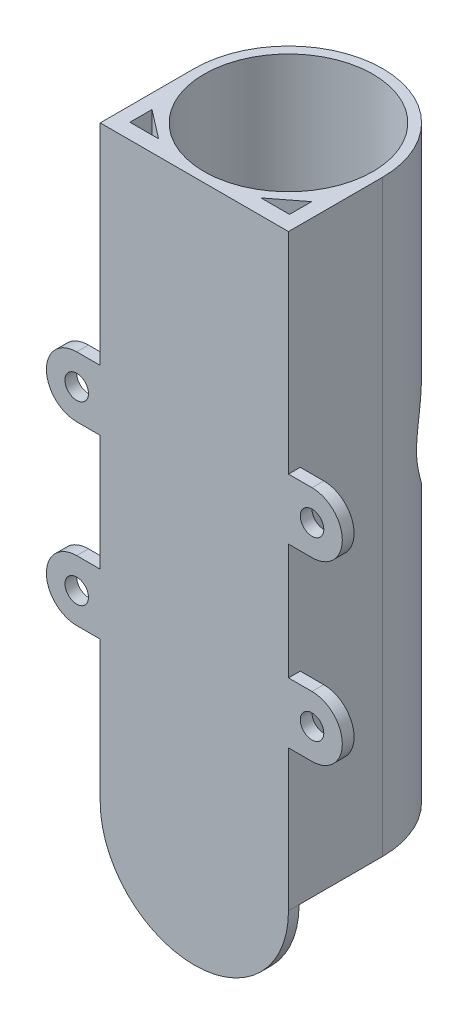
SolidWorks part; units mm, degrees
ref_plane "Front Plane" through (0, 0, 0) normal (0, 0, 1) x (1, 0, 0)
ref_plane "Top Plane" through (0, 0, 0) normal (0, 1, 0) x (1, 0, 0)
ref_plane "Right Plane" through (0, 0, 0) normal (1, 0, 0) x (0, 0, -1)
sketch "Sketch1" plane through (0, 0, 0) normal (0, 1, 0) x (1, 0, 0)
  line L0 (16, -16) -> (-16, -16)
  line L1 (-16, -16) -> (-16, 0)
  line L2 (0, -55) -> (0, 55) construction
  line L3 (16, -16) -> (16, 0)
  line L4 (-13.567, -13.3875) -> (-8.7, -13.3875)
  line L5 (-8.7, -13.3875) -> (-13.567, -9.6312)
  line L6 (-13.567, -9.6312) -> (-13.567, -13.3875)
  line L7 (13.567, -13.3875) -> (8.7, -13.3875)
  line L8 (8.7, -13.3875) -> (13.567, -9.6312)
  line L9 (13.567, -9.6312) -> (13.567, -13.3875)
  arc A0 (16, 0) -> (-16, 0) centre (0, 0) ccw
  circle A1 centre (0, 0) radius 14.35
  point P10 (0, -16)
  dimension "D1" = 32
  dimension "D2" = 1.65
extrude "Boss-Extrude1" add sketch "Sketch1" along normal blind 100
sketch "Sketch2" plane through (0, 0, 16) normal (0, 0, 1) x (1, 0, 0)
  line L0 (0, -55) -> (0, 55) construction
  circle A0 centre (0, 54.8666) radius 13.97
  dimension "D1" = 27.94
extrude "Cut-Extrude3" cut sketch "Sketch2" against normal mid plane 30 from offset 35 offset against normal yes
sketch "Sketch4" plane through (0, 0, 16) normal (0, 0, 1) x (1, 0, 0)
  line L0 (-16, 0) -> (16, 0)
  line L1 (-16, 100) -> (-16, 0) construction
  arc A0 (-16, 0) -> (16, 0) centre (0, 0) ccw
extrude "Boss-Extrude3" add sketch "Sketch4" against normal blind 1.8
sketch "Sketch5" plane through (0, 0, 0) normal (1, 0, 0) x (0, 0, -1)
  line L0 (-14.2, 0) -> (-16, -15.9552)
  line L1 (17.6, 0) -> (-17.6, 0) construction
  line L2 (-16, 0) -> (-16, -16) construction
  line L3 (-16, -15.9552) -> (-14.2, -16)
  line L4 (-14.2, -16) -> (-14.2, 0)
sketch "Sketch6" plane through (0, 0, 16) normal (0, 0, 1) x (1, 0, 0)
  line L0 (0, -17.6) -> (0, 17.6) construction
  line L5 (-9.2444, 34.2926) -> (-9.2444, 23.9926)
  line L6 (-20, 53.9921) -> (-9.2444, 53.9921)
  line L7 (-20, 64.2931) -> (-9.2444, 64.2931)
  line L8 (-20, 34.2926) -> (-9.2444, 34.2926)
  line L9 (-20, 23.9926) -> (-9.2444, 23.9926)
  line L10 (9.2444, 64.2931) -> (20, 64.2931)
  line L12 (9.2444, 64.2931) -> (9.2444, 53.9921)
  line L14 (-9.2444, 64.2931) -> (-9.2444, 53.9921)
  line L15 (9.2444, 34.2926) -> (9.2444, 23.9926)
  line L19 (9.2444, 53.9921) -> (20, 53.9921)
  line L20 (9.2444, 34.2926) -> (20, 34.2926)
  line L21 (9.2444, 23.9926) -> (20, 23.9926)
  circle A0 centre (-20, 29.1426) radius 2
  circle A1 centre (-20, 59.1426) radius 2
  circle A2 centre (20, 59.1426) radius 2
  circle A3 centre (20, 29.1426) radius 2
  arc A4 (-20, 64.2931) -> (-20, 53.9921) centre (-20, 59.1426) ccw
  arc A5 (-20, 34.2926) -> (-20, 23.9926) centre (-20, 29.1426) ccw
  arc A6 (20, 34.2926) -> (20, 23.9926) centre (20, 29.1426) cw
  arc A7 (20, 64.2931) -> (20, 53.9921) centre (20, 59.1426) cw
  point P0 (0, 49.1426)
  point P2 (0, 45.2106)
  dimension "D5" = 4
  dimension "D6" = 4
  dimension "D1" = 10.3
  dimension "D3" = 30
  dimension "D4" = 20
extrude "Boss-Extrude4" add sketch "Sketch6" against normal blind 2
